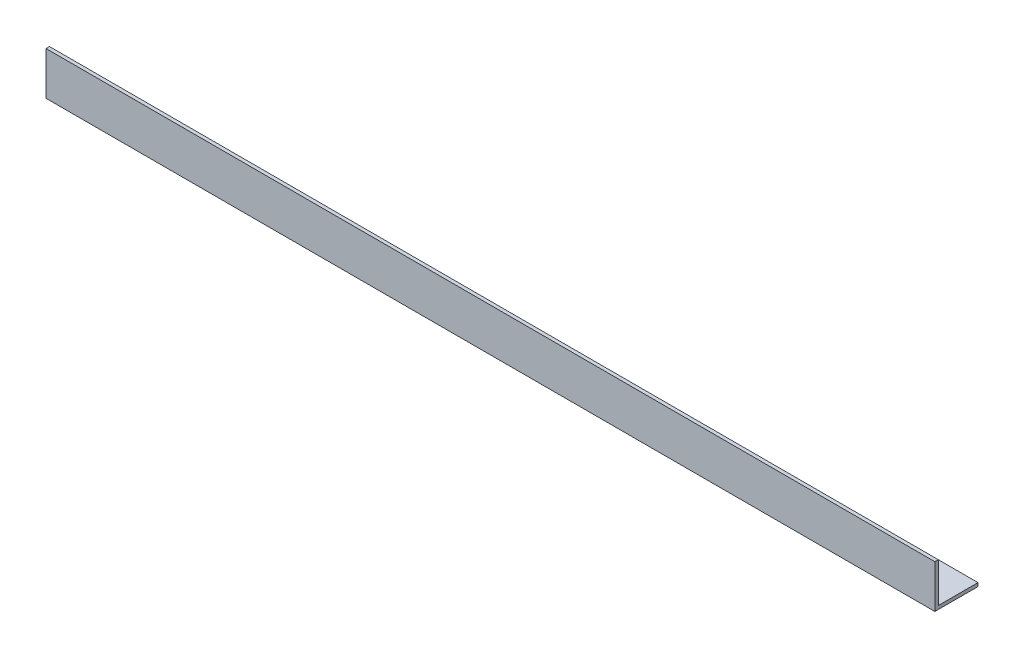
SolidWorks part; units mm, degrees
ref_plane "Спереди" through (0, 0, 0) normal (0, 0, 1) x (1, 0, 0)
ref_plane "Сверху" through (0, 0, 0) normal (0, 1, 0) x (1, 0, 0)
ref_plane "Справа" through (0, 0, 0) normal (1, 0, 0) x (0, 0, -1)
sketch "Эскиз1" plane through (0, 0, 0) normal (1, 0, 0) x (0, 0, -1)
  line L0 (0, 25) -> (0, 0)
  line L1 (0, 0) -> (25, 0)
extrude "Вытянуть-Тонкостенный1" add sketch "Эскиз1" along normal blind 515 thin thin type one direction reverse wall 2
